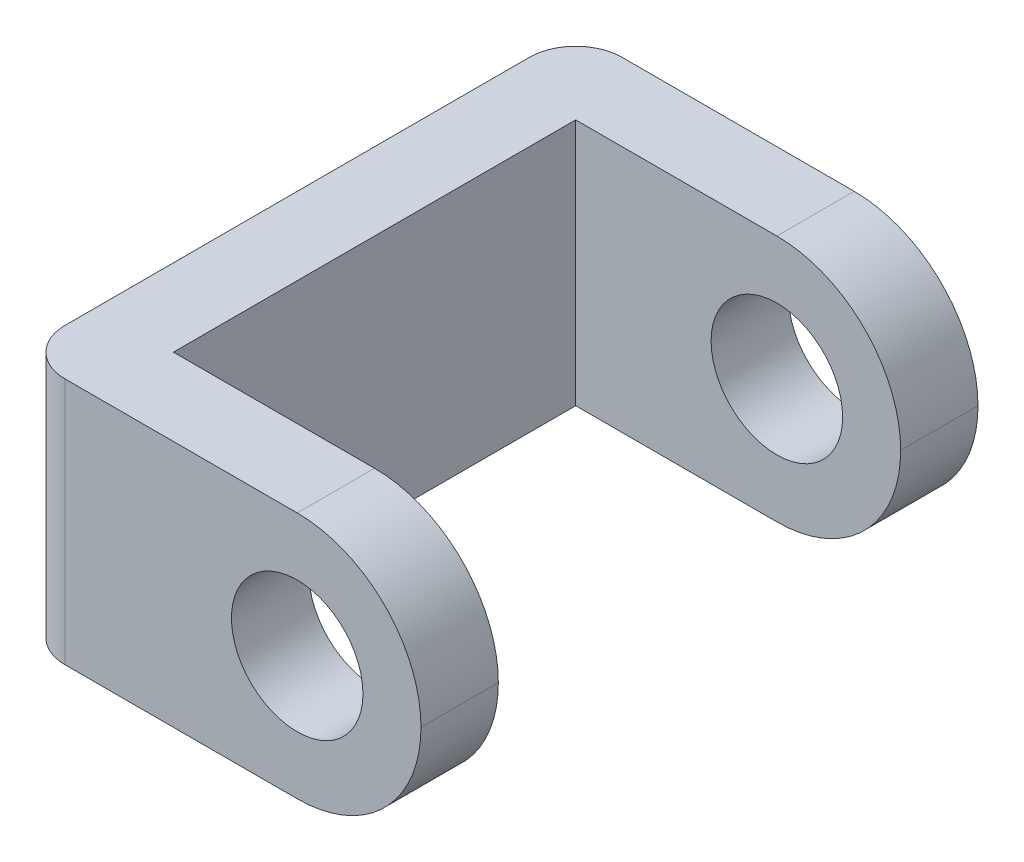
SolidWorks part; units mm, degrees
ref_plane "Спереди" through (0, 0, 0) normal (0, 0, 1) x (1, 0, 0)
ref_plane "Сверху" through (0, 0, 0) normal (0, 1, 0) x (1, 0, 0)
ref_plane "Справа" through (0, 0, 0) normal (1, 0, 0) x (0, 0, -1)
sketch "Эскиз1" plane through (0, 0, 0) normal (0, 1, 0) x (1, 0, 0)
  line L0 (0, 18) -> (0, -18)
  line L1 (0, -18) -> (26, -18)
  line L2 (26, -18) -> (26, -13)
  line L3 (26, -13) -> (5, -13)
  line L4 (5, -13) -> (5, 13)
  line L5 (5, 13) -> (26, 13)
  line L6 (26, 13) -> (26, 18)
  line L7 (26, 18) -> (0, 18)
  dimension "D1" = 36
  dimension "D2" = 5
  dimension "D3" = 18
  dimension "D4" = 5
  dimension "D5" = 26
  dimension "D6" = 5
extrude "Бобышка-Вытянуть1" add sketch "Эскиз1" along normal blind 16
fillet "Скругление1" radius 8 4 edges at (26, 0, -15.5) (26, 16, -15.5) (26, 0, 15.5) (26, 16, 15.5)
fillet "Скругление2" radius 3 2 edges at (0, 8, 18) (0, 8, -18)
sketch "Эскиз2" plane through (0, 0, 18) normal (0, 0, 1) x (1, 0, 0)
  circle A0 centre (18, 8) radius 4.25
  dimension "D1" = 8.5
extrude "Вырез-Вытянуть1" cut sketch "Эскиз2" against normal through all
